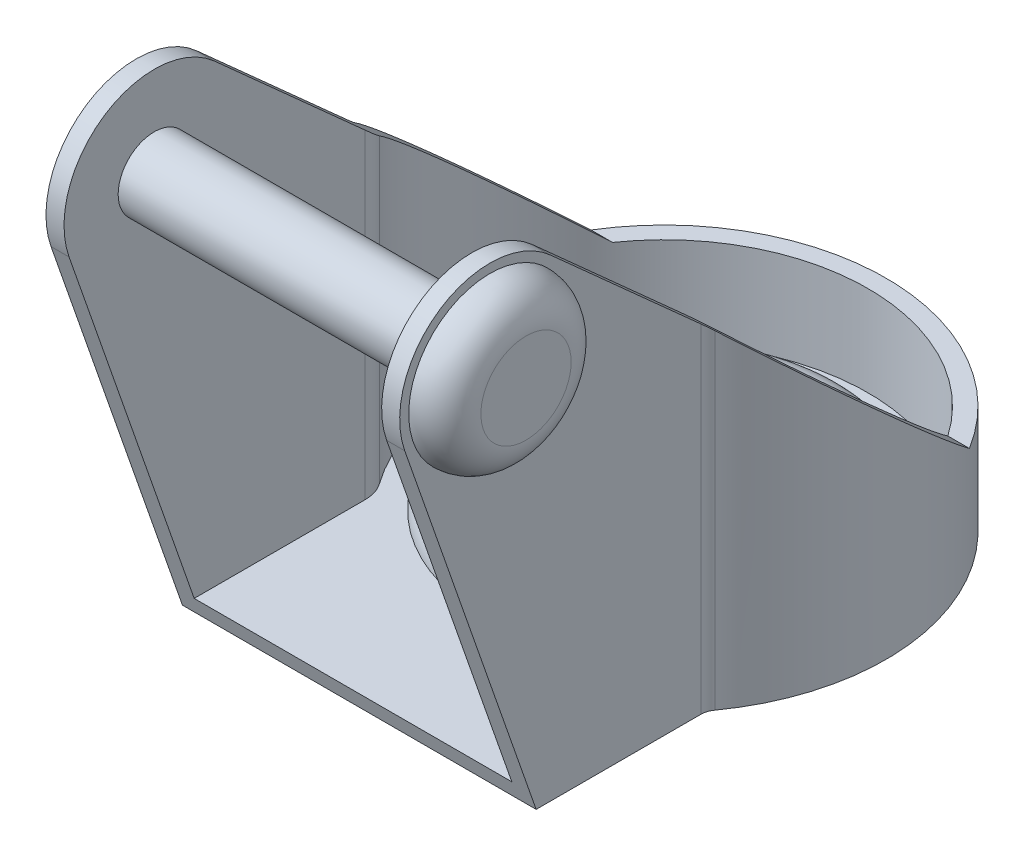
SolidWorks part; units mm, degrees
ref_plane "Front Plane" through (0, 0, 0) normal (0, 0, 1) x (1, 0, 0)
ref_plane "Top Plane" through (0, 0, 0) normal (0, 1, 0) x (1, 0, 0)
ref_plane "Right Plane" through (0, 0, 0) normal (1, 0, 0) x (0, 0, -1)
sketch "Sketch1" plane through (0, 0, 0) normal (0, 1, 0) x (1, 0, 0)
  line L0 (-9.8, -7.7621) -> (-9.8, -16.8887)
  line L2 (-8.8, -7.7621) -> (-8.8, -15.8887)
  line L3 (-8.8, -15.8887) -> (8.8, -15.8887)
  line L4 (8.8, -7.7621) -> (8.8, -15.8887)
  line L5 (0, -8.2053) -> (8.8, -15.8887) construction
  line L6 (-8.8, -15.8887) -> (0, -8.2053) construction
  line L7 (-9.8, -16.8887) -> (9.8, -16.8887)
  line L8 (9.8, -7.7621) -> (9.8, -16.8887)
  arc A0 (9.1759, -6.5949) -> (-9.1759, -6.5949) centre (0, 0) ccw
  arc A1 (-8.8, -7.7621) -> (-9.1759, -6.5949) centre (-10.8, -7.7621) ccw
  arc A2 (8.8, -7.7621) -> (9.1759, -6.5949) centre (10.8, -7.7621) cw
  arc A3 (9.988, -7.1785) -> (-9.988, -7.1785) centre (0, 0) ccw
  arc A4 (-9.8, -7.7621) -> (-9.988, -7.1785) centre (-10.8, -7.7621) ccw
  arc A5 (9.8, -7.7621) -> (9.988, -7.1785) centre (10.8, -7.7621) cw
  point P11 (-8.8, -7.0887)
  dimension "D1" = 22.6
  dimension "D4" = 2
  dimension "D5" = 2
  dimension "D2" = 17.6
  dimension "D3" = 8.8
  dimension "D6" = 1
extrude "Boss-Extrude3" add sketch "Sketch1" along normal blind 1 contours L4 A2 A0 A1 L2 L3 | L8 A5 A3 A4 L0 L7 A2 L4 L3 L2 A1 A0 region at (-9.4848, 0, 7.3385) region at (0, 0, 2.6277)
sketch "Sketch2" plane through (-9.8, 0, 0) normal (-1, 0, 0) x (0, 0, 1)
  line L0 (16.8887, 0) -> (24.172, 20.8512)
  line L1 (16.1136, 26.2225) -> (7.7621, 18.7335)
  line L4 (7.7621, 0) -> (16.8887, 0)
  line L5 (7.7621, 18.7335) -> (7.7621, 0)
  line L6 (7.7621, 18.7335) -> (-6.4334, 6.0039) construction
  line L7 (-6.4334, 6.0039) -> (-15.1437, 6.0039) construction
  line L8 (-15.1437, 6.0039) -> (-15.1437, 54.0238) construction
  line L9 (-15.1437, 54.0238) -> (16.1136, 54.0238) construction
  line L10 (16.1136, 54.0238) -> (16.1136, 26.2225) construction
  arc A0 (24.172, 20.8512) -> (16.1136, 26.2225) centre (19.4517, 22.5) ccw
  dimension "D1" = 22.5
  dimension "D2" = 5
extrude "Boss-Extrude4" add sketch "Sketch2" against normal up to surface (19.6 mm away) up to face at (9.8, 0.5, 12.3254)
sketch "Sketch4" plane through (0, 0, 0) normal (0, -1, 0) x (1, 0, 0)
  line L0 (8.8, 7.7621) -> (8.8, 15.8887) construction
  line L1 (-8.8, 7.7621) -> (-8.8, 15.8887) construction
  line L2 (8.8, 7.7621) -> (8.8, 15.8887)
  line L3 (-8.8, 7.7621) -> (-8.8, 15.8887)
  line L4 (-8.8, 15.8887) -> (-8.8, 29.0071)
  line L5 (-8.8, 29.0071) -> (8.8, 29.0071)
  line L6 (8.8, 29.0071) -> (8.8, 15.8887)
  line L7 (-8.8, 7.7621) -> (8.8, 7.7621)
extrude "Cut-Extrude3" cut sketch "Sketch4" against normal through all from offset 1 offset against normal yes
sketch "Sketch5" plane through (0, 1, 0) normal (0, 1, 0) x (1, 0, 0)
  line L2 (-8.8, -7.7621) -> (-9.8, -7.7621)
  line L3 (9.8, -7.7621) -> (8.8, -7.7621)
  arc A0 (-8.8, -7.7621) -> (-9.1759, -6.5949) centre (-10.8, -7.7621) ccw construction
  arc A1 (-9.8, -7.7621) -> (-9.988, -7.1785) centre (-10.8, -7.7621) ccw construction
  arc A2 (9.988, -7.1785) -> (-9.988, -7.1785) centre (0, 0) ccw construction
  arc A3 (9.988, -7.1785) -> (9.8, -7.7621) centre (10.8, -7.7621) ccw construction
  arc A4 (9.1759, -6.5949) -> (8.8, -7.7621) centre (10.8, -7.7621) ccw construction
  arc A5 (9.1759, -6.5949) -> (-9.1759, -6.5949) centre (0, 0) ccw construction
  arc A6 (-8.8, -7.7621) -> (-9.1759, -6.5949) centre (-10.8, -7.7621) ccw
  arc A7 (-9.8, -7.7621) -> (-9.988, -7.1785) centre (-10.8, -7.7621) ccw
  arc A8 (9.988, -7.1785) -> (-9.988, -7.1785) centre (0, 0) ccw
  arc A9 (9.988, -7.1785) -> (9.8, -7.7621) centre (10.8, -7.7621) ccw
  arc A10 (9.1759, -6.5949) -> (8.8, -7.7621) centre (10.8, -7.7621) ccw
  arc A11 (9.1759, -6.5949) -> (-9.1759, -6.5949) centre (0, 0) ccw
extrude "Boss-Extrude5" add sketch "Sketch5" along normal blind 30
sketch "Sketch7" plane through (0, 0, 0) normal (1, 0, 0) x (0, 0, -1)
  line L0 (15.1437, 54.0238) -> (-16.1136, 54.0238) construction
  line L3 (15.1437, 6.0039) -> (15.1437, 54.0238) construction
  line L4 (6.4334, 6.0039) -> (15.1437, 6.0039) construction
  line L5 (-7.7621, 18.7335) -> (6.4334, 6.0039) construction
  line L6 (-16.1136, 26.2225) -> (-7.7621, 18.7335) construction
  line L7 (-16.1136, 54.0238) -> (-16.1136, 26.2225) construction
  line L8 (15.1437, 54.0238) -> (-16.1136, 54.0238)
  line L9 (15.1437, 6.0039) -> (15.1437, 54.0238)
  line L10 (6.4334, 6.0039) -> (15.1437, 6.0039)
  line L11 (-7.7621, 18.7335) -> (6.4334, 6.0039)
  line L12 (-16.1136, 26.2225) -> (-7.7621, 18.7335)
  line L13 (-16.1136, 54.0238) -> (-16.1136, 26.2225)
extrude "Cut-Extrude4" cut sketch "Sketch7" against normal through all both and the other way through all
sketch "Sketch9" plane through (-8.8, 0, 0) normal (1, 0, 0) x (0, 0, -1)
  circle A0 centre (-19.4517, 22.5) radius 2
  dimension "D1" = 4
extrude "Boss-Extrude6" add sketch "Sketch9" along normal up to surface (17.6 mm away) up to face at (8.8, 14.1862, 15.026)
sketch "Sketch10" plane through (-9.8, 0, 0) normal (-1, 0, 0) x (0, 0, 1)
  circle A0 centre (19.4517, 22.5) radius 3.55
  dimension "D1" = 7.1
extrude "Boss-Extrude7" add sketch "Sketch10" along normal blind 1
sketch "Sketch11" plane through (-10.8, 0, 0) normal (-1, 0, 0) x (0, 0, 1)
  circle A0 centre (19.4517, 22.5) radius 1.8
  dimension "D1" = 3.6
extrude "Cut-Extrude5" cut sketch "Sketch11" against normal blind 2
sketch "Sketch12" plane through (9.8, 0, 0) normal (1, 0, 0) x (0, 0, -1)
  circle A0 centre (-19.4517, 22.5) radius 4.5
  dimension "D1" = 9
extrude "Boss-Extrude8" add sketch "Sketch12" along normal blind 2
sketch "Sketch13" plane through (0, 1, 0) normal (0, 1, 0) x (1, 0, 0)
  circle A0 centre (0, 0) radius 10.05
  circle A1 centre (0, 0) radius 5.1
  dimension "D1" = 10.2
  dimension "D2" = 20.1
extrude "Boss-Extrude9" add sketch "Sketch13" along normal blind 2
sketch "Sketch14" plane through (0, 1, 0) normal (0, 1, 0) x (1, 0, 0)
  circle A0 centre (0, 0) radius 2.6
  dimension "D1" = 5.2
extrude "Cut-Extrude6" cut sketch "Sketch14" against normal through all
fillet "Fillet2" radius 2 1 edges at (0, 3, 5.1) type face fillet first side face at (0, 3, 5.1) second side face at (0, 3, 10.05)
fillet "Fillet3" radius 2 1 edges at (0, 3, 10.05) type face fillet first side face at (0, 3, 10.05) second side face at (0, 3, 7.1)
fillet "Fillet4" radius 2 1 edges at (-10.8, 22.5, 23.0017)
fillet "Fillet5" radius 2 1 edges at (11.8, 22.5, 14.9517)
